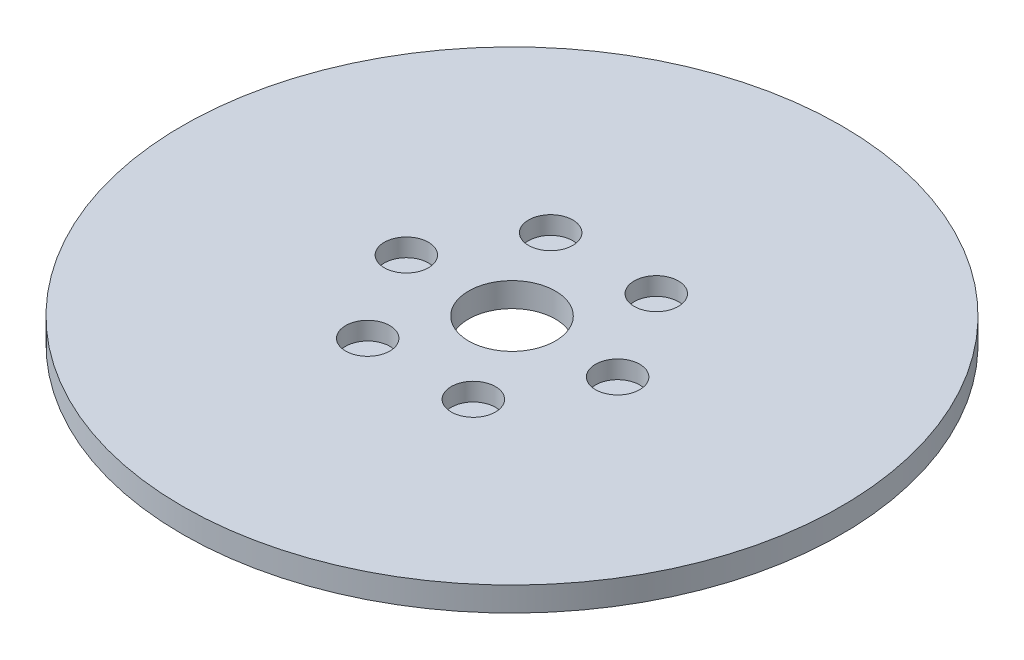
SolidWorks part; units mm, degrees
ref_plane "Front Plane" through (0, 0, 0) normal (0, 0, 1) x (1, 0, 0)
ref_plane "Top Plane" through (0, 0, 0) normal (0, 1, 0) x (1, 0, 0)
ref_plane "Right Plane" through (0, 0, 0) normal (1, 0, 0) x (0, 0, -1)
sketch "Sketch1" plane through (0, 0, 0) normal (0, 1, 0) x (1, 0, 0)
  circle A0 centre (0, 0) radius 95
  dimension "FLANGE_OD" = 190
extrude "Boss-Extrude1" add sketch "Sketch1" along normal blind 7
sketch "Sketch2" plane through (0, 0, 0) normal (0, 1, 0) x (1, 0, 0)
  circle A0 centre (0, 0) radius 12.5
  dimension "BORE_D" = 25
extrude "Cut-Extrude1" cut sketch "Sketch2" along normal through all
sketch "Sketch3" plane through (0, 7, 0) normal (0, 1, 0) x (1, 0, 0)
  circle A0 centre (0, 0) radius 30.4464 construction
  circle A1 centre (-30.4464, 0) radius 6.3696
  dimension "BOLT_D" = 12.7392
  dimension "BOLT_PCD" = 60.8929
extrude "Cut-Extrude2" cut sketch "Sketch3" against normal blind 5.1796
pattern_circular "CirPattern1" count 6 over 360 about axis through (0, 0, 0) along (0, 1, 0) of "Cut-Extrude2"
